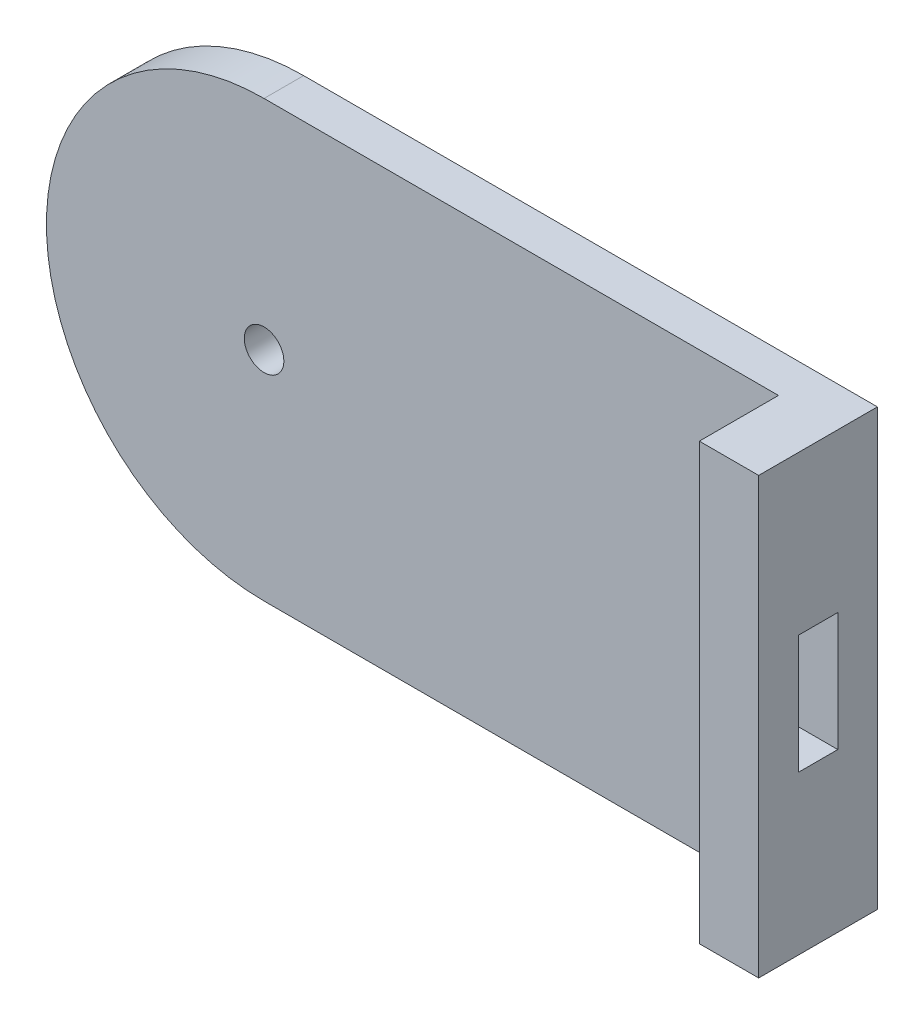
SolidWorks part; units mm, degrees
ref_plane "Front" through (0, 0, 0) normal (0, 0, 1) x (1, 0, 0)
ref_plane "Top" through (0, 0, 0) normal (0, 1, 0) x (1, 0, 0)
ref_plane "Right" through (0, 0, 0) normal (1, 0, 0) x (0, 0, -1)
sketch "Sketch1" plane through (0, 0, 0) normal (0, 0, 1) x (1, 0, 0)
  line L0 (-59.8185, 27.1774) -> (85.1815, 27.1774)
  line L1 (85.1815, 27.1774) -> (85.1815, -82.8226)
  line L2 (85.1815, -82.8226) -> (-59.8185, -82.8226)
  line L3 (70.1815, 27.1774) -> (70.1815, -82.8226)
  circle A0 centre (-59.8185, -27.8226) radius 5
  arc A1 (-62.4722, -37.4641) -> (-65.2125, -36.2431) centre (-59.8185, -27.8226) ccw construction
  arc A2 (-59.8185, -82.8226) -> (-59.8185, 27.1774) centre (-59.8185, -27.8226) cw
  dimension "D1" = 10
  dimension "D2" = 55
  dimension "D3" = 145
  dimension "D4" = 15
extrude "Boss-Extrude1" add sketch "Sketch1" against normal blind 10 contours A2 L2 L3 L0 A0 | L0 L3 L2 L1 region at (-16.6741, -27.8226, 0) region at (77.6815, -27.8226, 0)
extrude "Boss-Extrude2" add sketch "Sketch1<3>" along normal blind 20 contours L0 L3 L2 L1 region at (77.6815, -27.8226, 0)
sketch "Sketch1<3>" plane through (0, 0, 0) normal (0, 0, 1) x (1, 0, 0) same geometry as "Sketch1"
sketch "Sketch2" plane through (85.1815, 0, 0) normal (1, 0, 0) x (0, 0, -1)
  line L0 (0, -82.8226) -> (0, 27.1774) construction
  line L1 (-20, -27.8226) -> (10, -27.8226) construction
  line L3 (10, 27.1774) -> (10, -82.8226) construction
  line L4 (0, -42.8226) -> (0, -12.8226)
  line L5 (-10, -12.8226) -> (-10, -42.8226)
  line L6 (-10, -42.8226) -> (0, -42.8226)
  line L7 (-10, -12.8226) -> (0, -12.8226)
  line L8 (-20, 27.1774) -> (-20, -82.8226) construction
  point P10 (-10, -27.8226)
  dimension "D1" = 10
  dimension "D2" = 10
  dimension "D3" = 30
extrude "Cut-Extrude1" cut sketch "Sketch2" against normal blind 20
